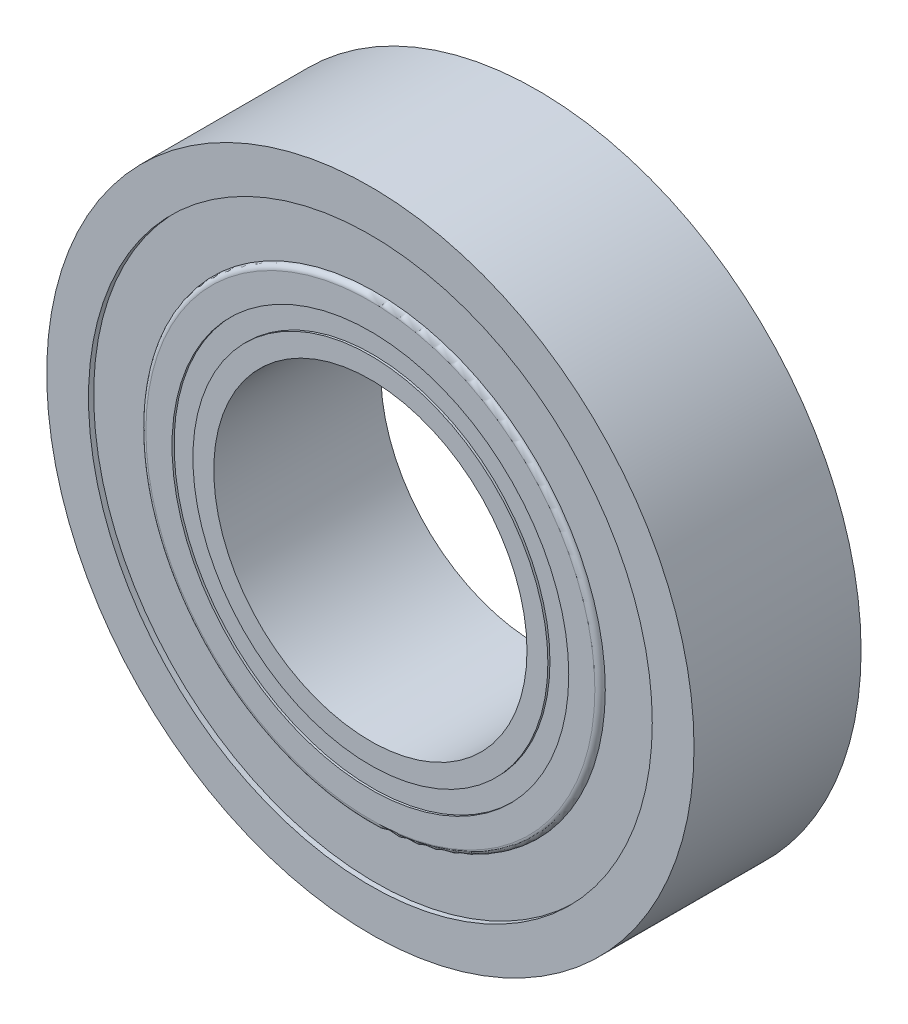
SolidWorks part; units mm, degrees
ref_plane "前视基准面" through (0, 0, 0) normal (0, 0, 1) x (1, 0, 0)
ref_plane "上视基准面" through (0, 0, 0) normal (0, 1, 0) x (1, 0, 0)
ref_plane "右视基准面" through (0, 0, 0) normal (1, 0, 0) x (0, 0, -1)
sketch "草图1" plane through (0, 0, 0) normal (0, 0, 1) x (1, 0, 0)
  circle A0 centre (0, 0) radius 15
  circle A1 centre (0, 0) radius 31
  dimension "D1" = 30
  dimension "D2" = 62
extrude "凸台-拉伸1" add sketch "草图1" along normal blind 16
sketch "草图2" plane through (0, 0, 16) normal (0, 0, 1) x (1, 0, 0)
  circle A0 centre (0, 0) radius 22
  circle A1 centre (0, 0) radius 27
  circle A2 centre (0, 0) radius 15 construction
  dimension "D1" = 5
  dimension "D2" = 7
extrude "切除-拉伸1" cut sketch "草图2" against normal blind 0.5
sketch "草图3" plane through (0, 0, 0) normal (0, 0, -1) x (-1, 0, 0)
  circle A0 centre (0, 0) radius 22
  circle A1 centre (0, 0) radius 27
  circle A2 centre (0, 0) radius 15 construction
  dimension "D1" = 5
  dimension "D2" = 7
extrude "切除-拉伸2" cut sketch "草图3" against normal blind 0.5
sketch "草图4" plane through (0, 0, 16) normal (0, 0, 1) x (1, 0, 0)
  circle A0 centre (0, 0) radius 17
  circle A1 centre (0, 0) radius 19
  circle A2 centre (0, 0) radius 15 construction
  dimension "D1" = 2
  dimension "D2" = 2
extrude "切除-拉伸3" cut sketch "草图4" against normal blind 0.2
fillet "圆角1" radius 0.5 2 edges at (-22, 0, 0) (22, 0, 16)
sketch "草图5" plane through (0, 0, 0) normal (0, 0, -1) x (-1, 0, 0)
  circle A0 centre (0, 0) radius 17
  circle A1 centre (0, 0) radius 19
  circle A2 centre (0, 0) radius 15 construction
  dimension "D1" = 2
  dimension "D2" = 2
extrude "切除-拉伸4" cut sketch "草图5" against normal blind 0.2
